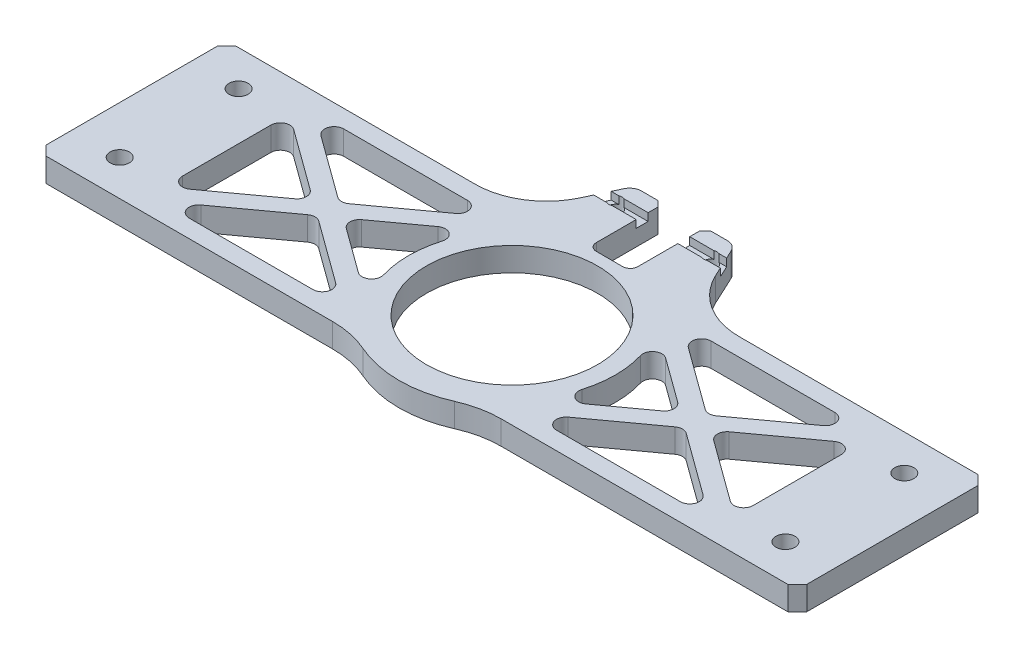
SolidWorks part; units mm, degrees
material "6061-T6 (SS)"
ref_plane "Front" through (0, 0, 0) normal (0, 0, 1) x (1, 0, 0)
ref_plane "Top" through (0, 0, 0) normal (0, 1, 0) x (1, 0, 0)
ref_plane "Right" through (0, 0, 0) normal (1, 0, 0) x (0, 0, -1)
sketch "Sketch1" plane through (0, 0, 0) normal (0, 1, 0) x (1, 0, 0)
  line L0 (203.2, 0) -> (203.2, 19.05) construction
  line L1 (0, 0) -> (79.0933, 0)
  line L2 (0, 0) -> (0, 50.8)
  line L3 (0, 50.8) -> (79.0933, 50.8)
  line L4 (203.2, 0) -> (203.2, 50.8)
  line L5 (0, 50.8) -> (203.2, 0) construction
  line L6 (124.1067, 50.8) -> (203.2, 50.8)
  line L7 (124.1067, 0) -> (203.2, 0)
  arc A0 (89.3821, -2.1771) -> (113.8179, -2.1771) centre (101.6, 25.4) ccw
  arc A1 (113.8179, 52.9771) -> (89.3821, 52.9771) centre (101.6, 25.4) ccw
  arc A2 (79.0933, 0) -> (89.3821, -2.1771) centre (79.0933, -25.4) cw
  arc A3 (124.1067, 0) -> (113.8179, -2.1771) centre (124.1067, -25.4) ccw
  arc A4 (124.1067, 50.8) -> (113.8179, 52.9771) centre (124.1067, 76.2) cw
  arc A5 (79.0933, 50.8) -> (89.3821, 52.9771) centre (79.0933, 76.2) ccw
  point P18 (117.867, 50.8)
  dimension "D2" = 60.325
  dimension "D3" = 25.4
  dimension "D1" = 50.8
extrude "Boss-Extrude1" add sketch "Sketch1" along normal blind 6.35
sketch "Sketch4" plane through (0, 6.35, 0) normal (0, 1, 0) x (1, 0, 0)
  line L0 (0, 0) -> (12.7, 9.525) construction
  line L1 (0, 0) -> (79.0933, 0) construction
  line L6 (12.7, 9.525) -> (12.7, 41.275) construction
  line L7 (12.7, 41.275) -> (25.4, 50.8) construction
  line L8 (79.0933, 50.8) -> (0, 50.8) construction
  line L9 (101.6, 0) -> (101.6, 25.4) construction
  arc A0 (89.3821, -2.1771) -> (113.8179, -2.1771) centre (101.6, 25.4) ccw construction
  point P0 (12.7, 41.275)
  point P4 (12.7, 9.525)
  point P34 (190.5, 9.525)
  point P36 (190.5, 41.275)
  dimension "D1" = 31.75
  dimension "D2" = 25.4
hole_wizard "#10 Clearance Hole1" positions "Sketch4" profile "Sketch3" hole size "#10" standard "ANSI Inch" end condition up to next
sketch "Sketch3" plane through (12.7, 6.35, -41.275) normal (1, 0, 0) x (0, 0, 1)
  line L0 (0, 0) -> (0, 6.35)
  line L1 (0, 6.35) -> (2.5527, 6.35)
  line L2 (2.5527, 6.35) -> (2.5527, 0)
  line L5 (2.5527, 0) -> (0, 0)
  line L11 (0, -6.35) -> (0, 107.95) construction
  dimension "Thru Hole Dia." = 5.1054
  dimension "Thru Hole Depth" = 6.35
sketch "Sketch5" plane through (0, 6.35, 0) normal (0, 1, 0) x (1, 0, 0)
  circle A0 centre (101.6, 25.4) radius 22.86
  arc A1 (113.8179, 52.9771) -> (89.3821, 52.9771) centre (101.6, 25.4) ccw construction
  dimension "D1" = 45.72
extrude "Cut-Extrude1" cut sketch "Sketch5" against normal through all
chamfer "Chamfer1" distance 2.54 angle 45 4 edges at (0, 3.175, -50.8) (203.2, 3.175, -50.8) (203.2, 3.175, 0) (0, 3.175, 0)
sketch "Sketch6" plane through (0, 6.35, 0) normal (0, 1, 0) x (1, 0, 0)
  line L1 (28.201, 46.0375) -> (76.8618, 46.0375)
  line L2 (25.4, 42.1858) -> (25.4, 8.6142)
  line L3 (28.201, 4.7625) -> (76.8618, 4.7625)
  line L9 (0, 48.26) -> (0, 2.54) construction
  line L10 (79.0933, 50.8) -> (2.54, 50.8) construction
  line L11 (2.54, 0) -> (79.0933, 0) construction
  line L14 (28.201, 46.0375) -> (52.5314, 28.3443)
  line L15 (76.8618, 4.7625) -> (52.5314, 22.4557)
  line L16 (76.8618, 46.0375) -> (52.5314, 28.3443)
  line L17 (28.201, 4.7625) -> (52.5314, 22.4557)
  line L18 (48.4826, 25.4) -> (25.4, 8.6142)
  line L19 (56.5802, 25.4) -> (79.6628, 42.1858)
  line L20 (56.5802, 25.4) -> (79.6628, 8.6142)
  line L21 (48.4826, 25.4) -> (25.4, 42.1858)
  line L22 (28.201, 46.0375) -> (25.4, 42.1858) construction
  line L23 (101.6, 25.4) -> (101.6, 40.5586) construction
  line L24 (76.8618, 4.7625) -> (79.6628, 8.6142) construction
  line L25 (154.7174, 25.4) -> (177.8, 42.1858)
  line L26 (146.6198, 25.4) -> (123.5372, 8.6142)
  line L27 (146.6198, 25.4) -> (123.5372, 42.1858)
  line L28 (154.7174, 25.4) -> (177.8, 8.6142)
  line L29 (174.999, 4.7625) -> (150.6686, 22.4557)
  line L30 (126.3382, 46.0375) -> (150.6686, 28.3443)
  line L31 (126.3382, 4.7625) -> (150.6686, 22.4557)
  line L32 (174.999, 46.0375) -> (150.6686, 28.3443)
  line L33 (174.999, 4.7625) -> (126.3382, 4.7625)
  line L34 (177.8, 42.1858) -> (177.8, 8.6142)
  line L35 (174.999, 46.0375) -> (126.3382, 46.0375)
  circle A6 centre (101.6, 25.4) radius 27.6225
  arc A7 (79.6628, 42.1858) -> (79.6628, 8.6142) centre (101.6, 25.4) ccw
  arc A8 (123.5372, 42.1858) -> (123.5372, 8.6142) centre (101.6, 25.4) cw
  dimension "D7" = 4.7625
  dimension "D1" = 4.7625
  dimension "D2" = 25.4
  dimension "D3" = 4.7625
  dimension "D4" = 4.7625
extrude "Cut-Extrude2" cut sketch "Sketch6" against normal through all
fillet "Fillet1" radius 2.54 24 edges at (76.8618, 3.175, -46.0375) (52.5314, 3.175, -28.3443) (150.6686, 3.175, -22.4557) (174.999, 3.175, -4.7625) (126.3382, 3.175, -4.7625) (177.8, 3.175, -42.1858) (177.8, 3.175, -8.6142) (154.7174, 3.175, -25.4) (150.6686, 3.175, -28.3443) (126.3382, 3.175, -46.0375) (174.999, 3.175, -46.0375) (28.201, 3.175, -4.7625) (52.5314, 3.175, -22.4557) (76.8618, 3.175, -4.7625) (56.5802, 3.175, -25.4) (79.6628, 3.175, -42.1858) (79.6628, 3.175, -8.6142) (25.4, 3.175, -42.1858) (48.4826, 3.175, -25.4) (25.4, 3.175, -8.6142) (146.6198, 3.175, -25.4) (123.5372, 3.175, -8.6142) (123.5372, 3.175, -42.1858) (28.201, 3.175, -46.0375)
sketch "Sketch7" plane through (0, 0, 0) normal (0, 1, 0) x (1, 0, 0)
  line L0 (83.6118, 61.7991) -> (87.2514, 69.6043)
  line L2 (90.1289, 71.4375) -> (94.5198, 71.4375)
  line L3 (96.0438, 69.9135) -> (96.0438, 55.0463)
  line L4 (119.5882, 61.7991) -> (115.9486, 69.6043)
  line L6 (113.0711, 71.4375) -> (108.6802, 71.4375)
  line L7 (107.1562, 69.9135) -> (107.1562, 55.0463)
  line L10 (79.0933, 50.8) -> (2.54, 50.8) construction
  line L11 (200.66, 50.8) -> (124.1067, 50.8) construction
  line L12 (79.0933, 50.8) -> (66.3466, 50.8)
  line L13 (136.8534, 50.8) -> (124.1067, 50.8)
  line L14 (94.5198, 71.4375) -> (96.0438, 69.9135)
  line L15 (108.6802, 71.4375) -> (107.1562, 69.9135)
  arc A0 (113.8179, 52.9771) -> (89.3821, 52.9771) centre (101.6, 25.4) ccw construction
  arc A3 (89.3821, -2.1771) -> (113.8179, -2.1771) centre (101.6, 25.4) ccw construction
  arc A5 (113.8179, 52.9771) -> (124.1067, 50.8) centre (124.1067, 76.2) ccw construction
  arc A6 (113.8179, 52.9771) -> (89.3821, 52.9771) centre (101.6, 25.4) ccw construction
  arc A7 (79.0933, 50.8) -> (89.3821, 52.9771) centre (79.0933, 76.2) ccw construction
  arc A8 (113.8179, 52.9771) -> (124.1067, 50.8) centre (124.1067, 76.2) ccw
  arc A9 (113.8179, 52.9771) -> (107.1562, 55.0463) centre (101.6, 25.4) ccw
  arc A14 (79.0933, 50.8) -> (89.3821, 52.9771) centre (79.0933, 76.2) ccw
  arc A15 (119.5882, 61.7991) -> (136.8534, 50.8) centre (136.8534, 69.85) ccw
  arc A22 (83.6118, 61.7991) -> (66.3466, 50.8) centre (66.3466, 69.85) cw
  arc A23 (96.0438, 55.0463) -> (89.3821, 52.9771) centre (101.6, 25.4) ccw
  arc A24 (115.9486, 69.6043) -> (113.0711, 71.4375) centre (113.0711, 68.2625) ccw
  arc A25 (87.2514, 69.6043) -> (90.1289, 71.4375) centre (90.1289, 68.2625) cw
  point P5 (96.0438, 71.4375)
  point P13 (107.1562, 71.4375)
  point P30 (88.1063, 71.4375)
  dimension "D4" = 19.05
  dimension "D6" = 3.175
  dimension "D1" = 11.1125
  dimension "D2" = 76.2
  dimension "D3" = 7.9375
  dimension "D5" = 50
extrude "Boss-Extrude2" add sketch "Sketch7" along normal up to surface (6.35 mm away) up to face at (134.6637, 6.35, -25.4)
sketch "Sketch8" plane through (0, 6.35, 0) normal (0, 1, 0) x (1, 0, 0)
  line L0 (87.2514, 69.6043) -> (83.6118, 61.7991) construction
  line L1 (84.701, 64.135) -> (118.499, 64.135)
  line L2 (84.701, 64.135) -> (84.701, 67.31)
  line L3 (84.701, 67.31) -> (118.499, 67.31)
  line L4 (118.499, 64.135) -> (118.499, 67.31)
  line L5 (119.5882, 61.7991) -> (115.9486, 69.6043) construction
  line L6 (118.499, 65.7225) -> (84.701, 65.7225) construction
  line L7 (101.6, 76.835) -> (101.6, 54.61) construction
  circle A1 centre (101.6, 25.4) radius 22.86 construction
  point P12 (101.6, 65.7225)
  dimension "D1" = 3.175
  dimension "D2" = 22.225
  dimension "D3" = 6.35
extrude "Cut-Extrude3" cut sketch "Sketch8" against normal blind 2.032
sketch "Sketch9" plane through (0, 6.35, 0) normal (0, 1, 0) x (1, 0, 0)
  line L0 (96.0438, 55.0463) -> (96.0438, 64.135) construction
  line L1 (96.0438, 71.4375) -> (107.1562, 71.4375)
  line L2 (96.0438, 71.4375) -> (96.0438, 53.467)
  line L3 (98.0758, 51.435) -> (105.1242, 51.435)
  line L4 (107.1562, 71.4375) -> (107.1562, 53.467)
  line L5 (107.1562, 64.135) -> (107.1562, 55.0463) construction
  line L6 (94.5198, 71.4375) -> (90.1289, 71.4375) construction
  circle A1 centre (101.6, 25.4) radius 22.86 construction
  arc A2 (105.1242, 51.435) -> (107.1562, 53.467) centre (105.1242, 53.467) ccw
  arc A3 (96.0438, 53.467) -> (98.0758, 51.435) centre (98.0758, 53.467) ccw
  point P5 (107.1562, 69.85)
  point P13 (0, 0)
  point P14 (0, 0)
  dimension "D2" = 2.032
  dimension "D1" = 3.175
extrude "Cut-Extrude4" cut sketch "Sketch9" against normal through all
sketch "Sketch12" plane through (0, 6.35, 0) normal (0, 1, 0) x (1, 0, 0)
  line L0 (88.9, 65.7225) -> (101.6, 25.4) construction
  line L1 (101.6, 25.4) -> (114.3, 65.7225) construction
  line L3 (118.499, 65.7225) -> (84.701, 65.7225) construction
  point P0 (88.9, 65.7225)
  point P2 (114.3, 65.7225)
  point P8 (86.5641, 64.6141)
  point P11 (0, 0)
  dimension "D1" = 25.4
hole_wizard "#8-32 Tapped Hole1" positions "Sketch12" profile "Sketch11" tap size "#8-32" standard "ANSI Inch" end condition up to next
sketch "Sketch11" plane through (88.9, 6.35, -65.7225) normal (1, 0, 0) x (0, 0, 1)
  line L0 (0, 0) -> (0, 6.35)
  line L1 (0, 6.35) -> (1.7272, 6.35)
  line L2 (1.7272, 6.35) -> (1.7272, 0)
  line L5 (1.7272, 0) -> (0, 0)
  line L11 (0, -6.35) -> (0, 107.95) construction
  dimension "Thru Tap Drill Dia." = 3.4544
  dimension "Thru Tap Drill Depth" = 6.35
cosmetic thread "Hole Thread4" parameters "D2"=4.1656
cosmetic thread "Hole Thread6" parameters "D2"=4.1656
